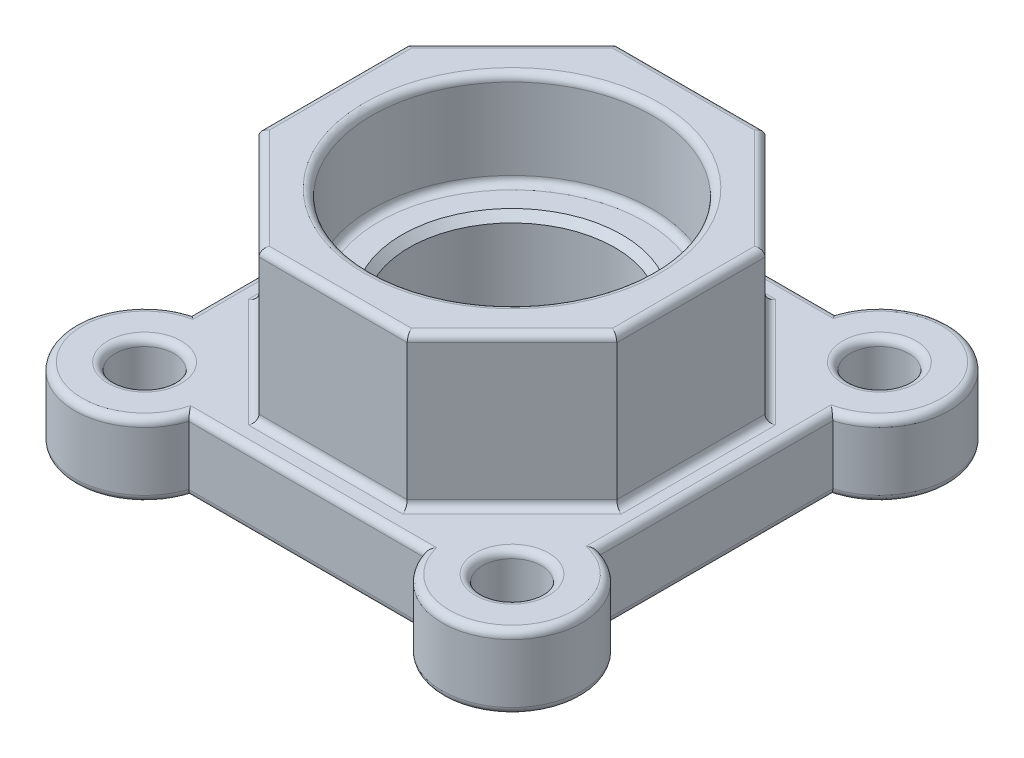
SolidWorks part; units mm, degrees
ref_plane "Front Plane" through (0, 0, 0) normal (0, 0, 1) x (1, 0, 0)
ref_plane "Top Plane" through (0, 0, 0) normal (0, 1, 0) x (1, 0, 0)
ref_plane "Right Plane" through (0, 0, 0) normal (1, 0, 0) x (0, 0, -1)
sketch "Sketch1" plane through (0, 0, 0) normal (0, 1, 0) x (1, 0, 0)
  line L1 (0, 0) -> (55.5, 0)
  line L2 (0, 0) -> (0, 56)
  line L3 (0, 56) -> (55.5, 56)
  line L4 (55.5, 0) -> (55.5, 56)
  dimension "D1" = 56
  dimension "D2" = 55.5
extrude "Boss-Extrude1" add sketch "Sketch1" along normal blind 10
sketch "Sketch2" plane through (0, 10, 0) normal (0, 1, 0) x (1, 0, 0)
  line L0 (0, 0) -> (55.5, 0) construction
  line L1 (0, 56) -> (0, 0) construction
  line L5 (55.5, 0) -> (55.5, 56) construction
  circle A0 centre (2.75, 3) radius 9.5
  circle A1 centre (2.75, 3) radius 4
  circle A2 centre (52.75, 3) radius 9.5
  circle A3 centre (52.75, 3) radius 4
  circle A4 centre (52.75, 53) radius 9.5
  circle A5 centre (52.75, 53) radius 4
  circle A6 centre (2.75, 53) radius 9.5
  circle A7 centre (2.75, 53) radius 4
  line M1 (0, 56) -> (0, 0)
  line M2 (0, 0) -> (55.5, 0)
  line M3 (55.5, 0) -> (55.5, 56)
  line M4 (55.5, 56) -> (0, 56)
  dimension "D1" = 8
  dimension "D2" = 9.5
  dimension "D3" = 3
  dimension "D4" = 2.75
  dimension "D7" = 50
  dimension "D8" = 50
  dimension "D9" = 3
  dimension "D10" = 2.75
  dimension "D5" = 2
  dimension "D6" = 2
extrude "Boss-Extrude2" add sketch "Sketch2" against normal blind 10 contours A7 A6 M4 M1 | A1 A0 M1 M2 | A3 A2 M2 M3 | A5 A4 M3 M4 region at (-0.2624, 10, -8.999) region at (-3.8715, 10, -59.4412) region at (46.9202, 10, 0.2624) region at (54.2276, 10, -62.1187)
extrude "Cut-Extrude1" cut sketch "Sketch2<3>" against normal blind 10 contours A7 M1 M4 | A5 M4 M3 | A3 M3 M2 | A1 M2 M1 region at (3.1426, 10, -3.2966) region at (3.1426, 10, -52.7034) region at (52.3574, 10, -3.2966) region at (52.3574, 10, -52.7034)
sketch "Sketch2<3>" plane through (0, 10, 0) normal (0, 1, 0) x (1, 0, 0) same geometry as "Sketch2"
fillet "Fillet1" radius 1 24 edges at (-4.0596, 0, -59.6241) (0, 0, -28) (-4.0596, 0, 3.6241) (27.75, 0, 0) (59.5596, 0, 3.6241) (55.5, 0, -28) (59.5596, 0, -59.6241) (27.75, 0, -56) (2.75, 0, -49) (52.75, 0, -49) (52.75, 0, 1) (2.75, 0, 1) (2.75, 10, -49) (2.75, 10, 1) (52.75, 10, 1) (52.75, 10, -49) (55.5, 10, -28) (59.5596, 10, 3.6241) (27.75, 10, 0) (-4.0596, 10, 3.6241) (0, 10, -28) (-4.0596, 10, -59.6241) (27.75, 10, -56) (59.5596, 10, -59.6241)
sketch "Sketch3" plane through (0, 10, 0) normal (0, 1, 0) x (1, 0, 0)
  line L0 (0, 12.0933) -> (0, 43.9067) construction
  line L1 (37.8361, 52.35) -> (17.6639, 52.35)
  line L2 (17.6639, 52.35) -> (3.4, 38.0861)
  line L3 (3.4, 38.0861) -> (3.4, 17.9139)
  line L4 (3.4, 17.9139) -> (17.6639, 3.65)
  line L5 (17.6639, 3.65) -> (37.8361, 3.65)
  line L6 (37.8361, 3.65) -> (52.1, 17.9139)
  line L7 (52.1, 17.9139) -> (52.1, 38.0861)
  line L8 (52.1, 38.0861) -> (37.8361, 52.35)
  line L9 (43.7361, 0) -> (11.7639, 0) construction
  circle A0 centre (27.75, 28) radius 24.35 construction
  circle A1 centre (27.75, 28) radius 19.1
  circle A2 centre (27.75, 28) radius 14
  circle A3 centre (27.75, 28) radius 12.5
  dimension "D3" = 48.7
  dimension "D4" = 38.2
  dimension "D5" = 28
  dimension "D6" = 25
  dimension "D1" = 27.75
  dimension "D2" = 28
extrude "Boss-Extrude3" add sketch "Sketch3" along normal blind 20.5 contours L7 L8 L1 L2 L3 L4 L5 L6 A1 region at (44.4811, 10, -44.7311)
extrude "Boss-Extrude4" add sketch "Sketch3<3>" along normal blind 7.5 contours A1 A2 region at (9.1902, 10, -28)
sketch "Sketch3<3>" plane through (0, 10, 0) normal (0, 1, 0) x (1, 0, 0) same geometry as "Sketch3"
extrude "Cut-Extrude2" cut sketch "Sketch3<4>" against normal blind 5.5 contours A2
sketch "Sketch3<4>" plane through (0, 10, 0) normal (0, 1, 0) x (1, 0, 0) same geometry as "Sketch3"
extrude "Cut-Extrude3" cut sketch "Sketch3<5>" against normal up to surface (10 mm away) contours A3 up to face at (27.75, 0, -28)
sketch "Sketch3<5>" plane through (0, 10, 0) normal (0, 1, 0) x (1, 0, 0) same geometry as "Sketch3"
chamfer "Chamfer1" distance 1 angle 45 1 edges at (27.75, 17.5, -14)
fillet "Fillet2" radius 1 8 edges at (3.4, 10, -28) (10.5319, 10, -45.2181) (27.75, 10, -52.35) (44.9681, 10, -45.2181) (52.1, 10, -28) (44.9681, 10, -10.7819) (27.75, 10, -3.65) (10.5319, 10, -10.7819)
fillet "Fillet3" radius 1 9 edges at (44.9681, 30.5, -10.7819) (27.75, 30.5, -3.65) (10.5319, 30.5, -10.7819) (3.4, 30.5, -28) (10.5319, 30.5, -45.2181) (27.75, 30.5, -52.35) (44.9681, 30.5, -45.2181) (52.1, 30.5, -28) (27.75, 30.5, -8.9)
fillet "Fillet4" radius 1 1 edges at (27.75, 17.5, -8.9)
fillet "Fillet5" radius 1 1 edges at (27.75, 4.5, -14)
chamfer "Chamfer2" distance 0.5 angle 70 1 edges at (27.75, 4.5, -15.5) first distance on face at (27.75, 4.5, -15)
